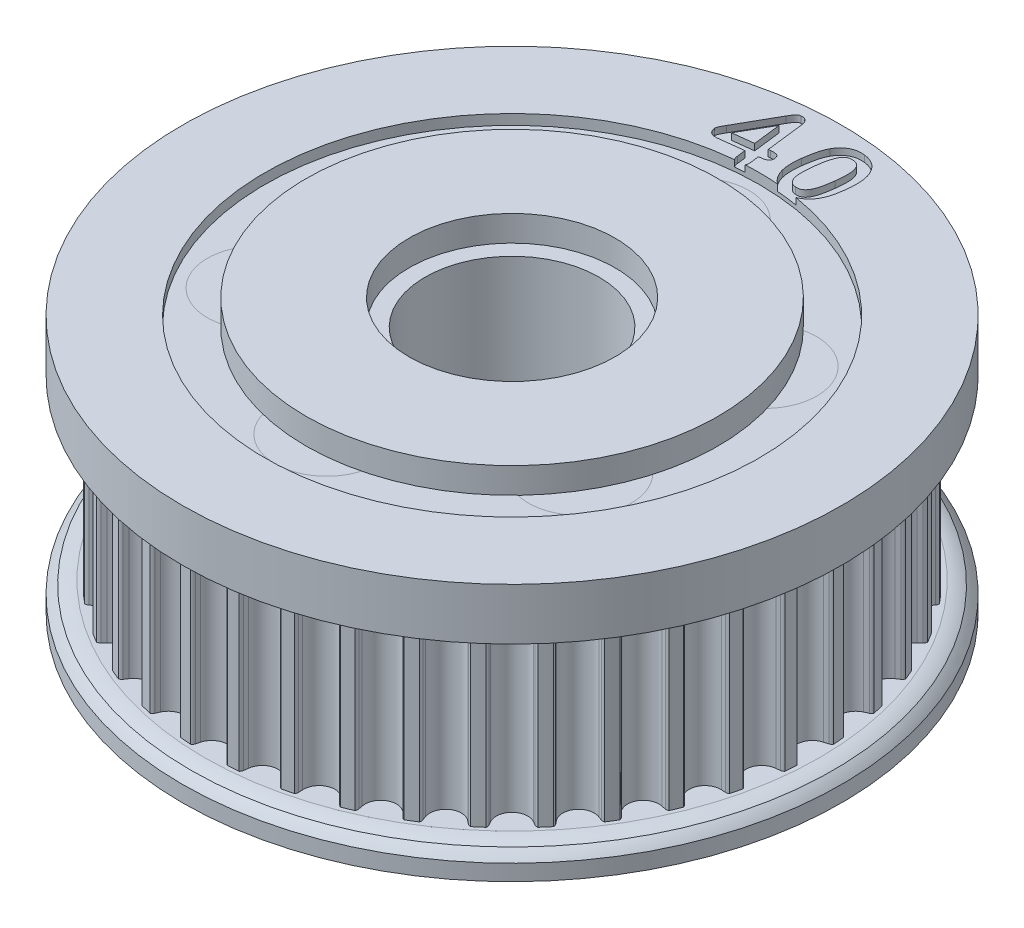
SolidWorks part; units mm, degrees
other "DetailItem2"
material "Markforged"
ref_plane "Front Plane" through (0, 0, 0) normal (0, 0, 1) x (1, 0, 0)
ref_plane "Top Plane" through (0, 0, 0) normal (0, 1, 0) x (1, 0, 0)
ref_plane "Right Plane" through (0, 0, 0) normal (1, 0, 0) x (0, 0, -1)
ref_axis "Centerline" through (0, 8.7312, 0) along (0, -1, 0)
sketch "Sketch1" plane through (0, 0, 0) normal (0, 1, 0) x (1, 0, 0)
  circle A0 centre (0, 0) radius 18.7176
  dimension "OuterDiameter" = 37.4352
extrude "ToothOD" add sketch "Sketch1" along normal mid plane 12.3825
sketch "Sketch2" plane through (0, 0, 0) normal (0, 1, 0) x (1, 0, 0)
  line L0 (0, 17.5492) -> (50000, 17.5492) construction
  line L1 (0, 18.7176) -> (50000, 18.7176) construction
  line L2 (0, 0) -> (0, 50000) construction
  arc A0 (-0.937, 18.2677) -> (0, 17.5492) centre (0, 18.5195) ccw
  arc A1 (-1.1278, 18.6836) -> (1.1278, 18.6836) centre (0, 0) cw
  circle A2 centre (0, 0) radius 18.7176 construction
  arc A3 (-0.937, 18.2677) -> (-1.0078, 18.5195) centre (-11.9754, 15.3012) ccw
  arc A4 (-1.0078, 18.5195) -> (-1.1278, 18.6836) centre (-1.2954, 18.4351) ccw
  circle A5 centre (0, 0) radius 18.7176 construction
  arc A6 (0.937, 18.2677) -> (1.0078, 18.5195) centre (11.9754, 15.3012) cw
  arc A7 (1.0078, 18.5195) -> (1.1278, 18.6836) centre (1.2954, 18.4351) cw
  arc A8 (0, 17.5492) -> (0.937, 18.2677) centre (0, 18.5195) ccw
  dimension "D1" = 1.9406
  dimension "D3" = 22.86
  dimension "D4" = 0.5994
  dimension "D2" = 1.1684
  dimension "D5" = 1.2954
extrude "ToothProfile" cut sketch "Sketch2" against normal through all both and the other way through all
pattern_circular "ToothPattern" count 40 over 360 about axis through (0, 6.1913, 0) along (0, -1, 0) of "ToothProfile"
sketch "Sketch4" plane through (0, 0, 0) normal (0, 0, 1) x (1, 0, 0)
  line L0 (0, -6.1913) -> (18.9716, -6.1913)
  line L1 (0, -7.9375) -> (20.32, -7.9375)
  line L2 (0, -7.9375) -> (0, -6.1913)
  line L3 (20.32, -7.9375) -> (20.32, -6.9532)
  line L4 (0, 0) -> (50000, 0) construction
  line L5 (20.32, 7.9375) -> (20.32, 6.9532)
  line L6 (0, 7.9375) -> (0, 6.1913)
  line L7 (0, 7.9375) -> (20.32, 7.9375)
  line L8 (0, 6.1913) -> (18.9716, 6.1913) construction
  line L9 (0, 6.1913) -> (0, 3.9688)
  line L10 (0, 3.9688) -> (18.9716, 3.9688)
  line L11 (18.9716, 3.9688) -> (20.32, 4.7473)
  line L12 (20.32, 4.7473) -> (20.32, 6.9532)
  line L13 (18.9716, 3.9688) -> (18.9716, 6.1913) construction
  arc A0 (18.9716, -6.1913) -> (19.812, -6.4452) centre (18.6641, -8.7261) cw
  arc A2 (19.812, -6.4452) -> (20.32, -6.9532) centre (17.815, -8.9503) cw
  arc A3 (19.812, 6.4452) -> (20.32, 6.9532) centre (17.815, 8.9503) ccw construction
  arc A4 (18.9716, 6.1913) -> (19.812, 6.4452) centre (18.6641, 8.7261) ccw construction
  dimension "D5" = 2.5534
  dimension "D6" = 3.2036
  dimension "FlangeID" = 18.9716
  dimension "D1" = 1.7463
  dimension "D2" = 0.9843
  dimension "D3" = 6.1913
  dimension "D4" = 15.875
  dimension "D7" = 0.762
  dimension "D8" = 0.508
  dimension "D10" = 0.508
  dimension "D9" = 20.32
  dimension "D11" = 10.16
  dimension "D12" = 30
revolve "Flange" add sketch "Sketch4" angle 360 about axis through (0, 8.7312, 0) along (0, -1, 0)
sketch "Sketch7" plane through (0, 0, 0) normal (0, -1, 0) x (1, 0, 0)
  circle A0 centre (0, 0) radius 5.3581
  dimension "D1" = 10.7163
extrude "Bore" cut sketch "Sketch7" against normal through all both and the other way through all
sketch "Sketch9" plane through (0, 7.9375, 0) normal (0, 1, 0) x (1, 0, 0)
  arc A0 (-10.7763, -10.7763) -> (10.7763, -10.7763) centre (0, 0) cw construction
  text T0 "40" font "Arial Rounded MT Bold" height 4.572
  point P3 (0, 15.24)
  dimension "D1" = 15.24
  dimension "D2" = 270
extrude "Large Tooth Count" cut sketch "Sketch9" against normal blind 0.4 and the other way through all
sketch "Sketch11" plane through (0, 7.9375, 0) normal (0, 1, 0) x (1, 0, 0)
  arc A0 (-4.8314, -4.8314) -> (4.8314, -4.8314) centre (0, 0) cw construction
  text T0 "<b>40</b>" font "Arial Rounded MT Bold" height 2.286
  point P6 (0, 6.8326)
  dimension "D4" = 6.8326
  dimension "D3" = 270
extrude "Small Tooth Count" [suppressed] cut sketch "Sketch11" against normal blind 0.4 and the other way through all
sketch "Sketch14" plane through (0, 0, 0) normal (0, 0, 1) x (1, 0, 0)
  line L0 (20.32, 7.9375) -> (-20.32, 7.9375) construction
  line L1 (0, 7.9375) -> (15.24, 7.9375)
  line L2 (0, 7.9375) -> (0, 7.3025)
  line L3 (0, 7.3025) -> (15.24, 7.3025)
  line L4 (15.24, 7.9375) -> (15.24, 7.3025)
  line L5 (0, 7.9375) -> (15.24, 7.3025) construction
  line L6 (0, 7.3025) -> (15.24, 7.9375) construction
  line L7 (-20.32, -7.9375) -> (20.32, -7.9375) construction
  line L8 (0, -7.9375) -> (15.24, -7.9375)
  line L9 (0, -7.9375) -> (0, -2.2225)
  line L10 (0, -2.2225) -> (15.24, -2.2225)
  line L11 (15.24, -7.9375) -> (15.24, -2.2225)
  line L12 (0, -7.9375) -> (15.24, -2.2225) construction
  line L13 (0, -2.2225) -> (15.24, -7.9375) construction
  line L14 (0, 0) -> (0, 50000) construction
  point P4 (7.62, 7.62)
  point P11 (7.62, -5.08)
  dimension "D1" = 9.525
  dimension "D2" = 15.24
  dimension "D3" = 10.16
revolve "Cut-Revolve1" cut sketch "Sketch14" angle 360 about L14
sketch "Sketch15" plane through (0, -7.9375, 0) normal (0, -1, 0) x (1, 0, 0)
  line L0 (0, 0) -> (0, 11.43) construction
  line L1 (-3.175, 0) -> (-3.175, 11.43)
  line L2 (3.175, 0) -> (3.175, 11.43)
  arc A0 (-3.175, 0) -> (3.175, 0) centre (0, 0) ccw
  arc A1 (3.175, 11.43) -> (-3.175, 11.43) centre (0, 11.43) ccw
  point P3 (0, 5.715)
  dimension "D1" = 3.175
  dimension "D2" = 11.43
extrude "Cut-Extrude1" cut sketch "Sketch15" against normal through all
pattern_circular "CirPattern1" count 6 over 360 about axis through (0, 7.9375, 0) along (0, -1, 0) of "Cut-Extrude1"
fillet "Fillet1" radius 3.175 6 edges at (-6.35, 2.54, 0) (-3.175, 2.54, -5.4993) (3.175, 2.54, -5.4993) (6.35, 2.54, 0) (-3.175, 2.54, 5.4993) (3.175, 2.54, 5.4993)
sketch "Sketch17" plane through (0, -2.2225, 0) normal (0, -1, 0) x (1, 0, 0)
  line L14 (3.175, 10.9985) -> (3.175, 11.43)
  line L16 (8.3112, 8.4646) -> (7.9375, 8.2489)
  line L18 (11.1125, 2.7496) -> (11.4862, 2.9654)
  line L20 (11.4862, -2.9654) -> (11.1125, -2.7496)
  line L22 (7.9375, -8.2489) -> (8.3112, -8.4646)
  line L24 (3.175, -11.43) -> (3.175, -10.9985)
  line L26 (-3.175, -10.9985) -> (-3.175, -11.43)
  line L28 (-8.3112, -8.4646) -> (-7.9375, -8.2489)
  line L30 (-11.1125, -2.7496) -> (-11.4862, -2.9654)
  line L32 (-11.4862, 2.9654) -> (-11.1125, 2.7496)
  line L34 (-7.9375, 8.2489) -> (-8.3112, 8.4646)
  line L37 (-3.175, 11.43) -> (-3.175, 10.9985)
  line L50 (3.175, 10.9985) -> (3.175, 11.43)
  line L51 (8.3112, 8.4646) -> (7.9375, 8.2489)
  line L52 (11.1125, 2.7496) -> (11.4862, 2.9654)
  line L53 (11.4862, -2.9654) -> (11.1125, -2.7496)
  line L54 (7.9375, -8.2489) -> (8.3112, -8.4646)
  line L55 (3.175, -11.43) -> (3.175, -10.9985)
  line L56 (-3.175, -10.9985) -> (-3.175, -11.43)
  line L57 (-8.3112, -8.4646) -> (-7.9375, -8.2489)
  line L58 (-11.1125, -2.7496) -> (-11.4862, -2.9654)
  line L59 (-11.4862, 2.9654) -> (-11.1125, 2.7496)
  line L60 (-7.9375, 8.2489) -> (-8.3112, 8.4646)
  line L61 (-3.175, 11.43) -> (-3.175, 10.9985)
  circle A1 centre (0, 0) radius 5.3581 construction
  circle A8 centre (0, 0) radius 5.3581
  arc A47 (3.175, 10.9985) -> (7.9375, 8.2489) centre (6.35, 10.9985) ccw
  arc A48 (11.4862, 2.9654) -> (8.3112, 8.4646) centre (9.8987, 5.715) ccw
  arc A49 (11.1125, 2.7496) -> (11.1125, -2.7496) centre (12.7, 0) ccw
  arc A50 (8.3112, -8.4646) -> (11.4862, -2.9654) centre (9.8987, -5.715) ccw
  arc A51 (7.9375, -8.2489) -> (3.175, -10.9985) centre (6.35, -10.9985) ccw
  arc A52 (-3.175, -11.43) -> (3.175, -11.43) centre (0, -11.43) ccw
  arc A53 (-3.175, -10.9985) -> (-7.9375, -8.2489) centre (-6.35, -10.9985) ccw
  arc A54 (-11.4862, -2.9654) -> (-8.3112, -8.4646) centre (-9.8987, -5.715) ccw
  arc A55 (-11.1125, -2.7496) -> (-11.1125, 2.7496) centre (-12.7, 0) ccw
  arc A56 (-8.3112, 8.4646) -> (-11.4862, 2.9654) centre (-9.8987, 5.715) ccw
  arc A57 (-7.9375, 8.2489) -> (-3.175, 10.9985) centre (-6.35, 10.9985) ccw
  arc A70 (3.175, 11.43) -> (-3.175, 11.43) centre (0, 11.43) ccw
  arc A71 (3.175, 10.9985) -> (7.9375, 8.2489) centre (6.35, 10.9985) ccw
  arc A72 (11.4862, 2.9654) -> (8.3112, 8.4646) centre (9.8987, 5.715) ccw
  arc A73 (11.1125, 2.7496) -> (11.1125, -2.7496) centre (12.7, 0) ccw
  arc A74 (8.3112, -8.4646) -> (11.4862, -2.9654) centre (9.8987, -5.715) ccw
  arc A75 (7.9375, -8.2489) -> (3.175, -10.9985) centre (6.35, -10.9985) ccw
  arc A76 (-3.175, -11.43) -> (3.175, -11.43) centre (0, -11.43) ccw
  arc A77 (-3.175, -10.9985) -> (-7.9375, -8.2489) centre (-6.35, -10.9985) ccw
  arc A78 (-11.4862, -2.9654) -> (-8.3112, -8.4646) centre (-9.8987, -5.715) ccw
  arc A79 (-11.1125, -2.7496) -> (-11.1125, 2.7496) centre (-12.7, 0) ccw
  arc A80 (-8.3112, 8.4646) -> (-11.4862, 2.9654) centre (-9.8987, 5.715) ccw
  arc A81 (-7.9375, 8.2489) -> (-3.175, 10.9985) centre (-6.35, 10.9985) ccw
  arc A82 (3.175, 11.43) -> (-3.175, 11.43) centre (0, 11.43) ccw
  dimension "D1" = 0
extrude "Boss-Extrude1" add sketch "Sketch17" against normal up to surface (9.525 mm away) separate body up to face at (0, 7.3025, 0)
sketch "Sketch21" plane through (0, -2.2225, 0) normal (0, -1, 0) x (1, 0, 0)
  circle A0 centre (0, 0) radius 7.9375
  dimension "D1" = 15.875
extrude "Cut-Extrude4" cut sketch "Sketch21" against normal blind 2.286
chamfer "Chamfer1" distance 2.54 angle 45 1 edges at (0, -7.9375, -15.24)
chamfer "Chamfer2" distance 0.635 angle 45 1 edges at (0, -2.2225, -15.24)
sketch "Sketch22" plane through (0, 7.3025, 0) normal (0, 1, 0) x (1, 0, 0)
  circle A0 centre (0, 0) radius 6.35
  circle A1 centre (0, 0) radius 12.7
  dimension "D1" = 12.7
  dimension "D2" = 25.4
extrude "Boss-Extrude2" add sketch "Sketch22" along normal blind 1.5875 separate body
equation "\"OuterDiameter@Sketch1\"= \"OD\""
equation "\"Teeth\"= \"No_Teeth\""
equation "\"PD\"= \"No_Teeth\" * 3mm / pi"
equation "\"OD\"= \"PD\" - .030"
equation "\"ToothCount@ToothPattern\" = \"Teeth\""
equation "\"Angle\"= 360 / \"Teeth\""
equation "\"AngleSpacing@ToothPattern\" = \"Angle\""
equation "\"FlangeID@Sketch4\"=\"OD\"/2+.01"
equation "\"D3@Sketch4\"=\"Tooth_Face_Length\"/2"
equation "\"Bearing_Feature\"= \"Bearing_Boss\""
equation "\"TopBearingBoss\" = IIF ( \"Bearing_Feature\" > 0 , \"unsuppressed\" , \"suppressed\" )"
equation "\"HexBore\"= \"Hex_Bore\" + \"Print_Tolerance\""
equation "\"Large Tooth Count\" = iif ( \"No_Teeth\" < \"TextTooth\" , \"suppressed\" , \"unsuppressed\" )"
equation "\"Small Tooth Count\"= iif ( \"No_Teeth\" < \"TextTooth\" , \"unsuppressed\" , \"suppressed\" )"
equation "\"BottomBearingBoss\" = iif ( \"Bearing_Feature\" > 1 , \"unsuppressed\" , \"suppressed\" )"
equation "\"ToothFaceLength@ToothOD\" = \"Tooth_Face_Length\""
equation "\"D4@Sketch4\" = \"Width_No_BearingBoss\""
equation "\"TextTooth\"= iif ( \"Hex_Bore\" <= .380 , 23 , iif ( \"Hex_Bore\" <= .505 , 25 , 16 ) )"
equation "\"D4@Sketch11\"=\"HexBore\"/2+.08"
